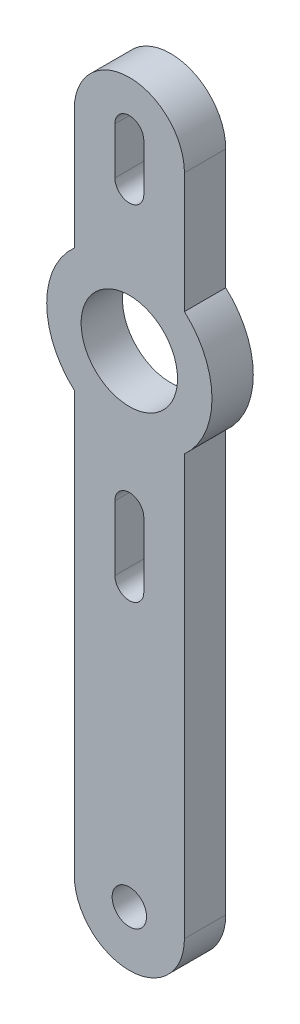
SolidWorks part; units mm, degrees
ref_plane "Plan de face" through (0, 0, 0) normal (0, 0, 1) x (1, 0, 0)
ref_plane "Plan de dessus" through (0, 0, 0) normal (0, 1, 0) x (1, 0, 0)
ref_plane "Plan de droite" through (0, 0, 0) normal (1, 0, 0) x (0, 0, -1)
sketch "Esquisse1" plane through (0, 0, 0) normal (0, 0, 1) x (1, 0, 0)
  line L0 (316.2402, 1609.0162) -> (317.0043, 1552.8214) construction
  line L1 (312.5454, 1587.3485) -> (312.5454, 1556.8582)
  line L2 (312.5454, 1605.0247) -> (312.5454, 1596.2927)
  line L3 (320.5454, 1587.3485) -> (320.5454, 1556.8582)
  line L4 (320.5454, 1605.0247) -> (320.5454, 1596.2927)
  line L5 (312.5454, 1580.4454) -> (320.5454, 1580.4454) construction
  line L6 (316.5454, 1580.4454) -> (316.5454, 1612.014) construction
  line L7 (316.5454, 1580.4454) -> (316.5454, 1554.1767) construction
  line L8 (316.5454, 1605.0247) -> (316.5454, 1602.7247) construction
  line L9 (318.1454, 1605.0247) -> (318.1454, 1602.7247) construction
  line L10 (314.9454, 1605.0247) -> (314.9454, 1602.7247) construction
  line L11 (315.4954, 1605.5747) -> (315.4954, 1602.1747)
  line L12 (315.4954, 1606.6247) -> (317.5954, 1606.6247) construction
  line L13 (315.4954, 1606.6247) -> (315.4954, 1601.1247) construction
  line L14 (315.4954, 1601.1247) -> (317.5954, 1601.1247) construction
  line L15 (317.5954, 1606.6247) -> (317.5954, 1601.1247) construction
  line L16 (317.5954, 1605.5747) -> (317.5954, 1602.1747)
  line L17 (315.4954, 1581.8706) -> (315.4954, 1577.1706)
  line L18 (315.4954, 1582.9206) -> (317.5954, 1582.9206) construction
  line L19 (315.4954, 1582.9206) -> (315.4954, 1576.1206) construction
  line L20 (315.4954, 1576.1206) -> (317.5954, 1576.1206) construction
  line L21 (317.5954, 1582.9206) -> (317.5954, 1576.1206) construction
  line L22 (317.5954, 1581.8706) -> (317.5954, 1577.1706)
  circle A0 centre (316.5454, 1605.0247) radius 4 construction
  circle A1 centre (316.5454, 1591.8206) radius 3.5
  circle A2 centre (316.5454, 1591.8206) radius 6 construction
  circle A3 centre (316.5454, 1556.8582) radius 1.25
  circle A4 centre (316.5454, 1556.8582) radius 4 construction
  arc A5 (312.5454, 1596.2927) -> (312.5454, 1587.3485) centre (316.5454, 1591.8206) ccw
  arc A6 (320.5454, 1596.2927) -> (320.5454, 1587.3485) centre (316.5454, 1591.8206) cw
  arc A7 (312.5454, 1605.0247) -> (320.5454, 1605.0247) centre (316.5454, 1605.0247) cw
  arc A8 (312.5454, 1556.8582) -> (320.5454, 1556.8582) centre (316.5454, 1556.8582) ccw
  arc A9 (318.1454, 1605.0247) -> (314.9454, 1605.0247) centre (316.5454, 1605.0247) ccw construction
  arc A10 (314.9454, 1602.7247) -> (318.1454, 1602.7247) centre (316.5454, 1602.7247) ccw construction
  arc A11 (317.5954, 1605.5747) -> (315.4954, 1605.5747) centre (316.5454, 1605.5747) ccw
  arc A13 (315.4954, 1602.1747) -> (317.5954, 1602.1747) centre (316.5454, 1602.1747) ccw
  arc A14 (317.5954, 1581.8706) -> (315.4954, 1581.8706) centre (316.5454, 1581.8706) ccw
  arc A15 (315.4954, 1577.1706) -> (317.5954, 1577.1706) centre (316.5454, 1577.1706) ccw
  point P28 (316.5454, 1603.8747)
  point P38 (316.5454, 1609.0247)
  dimension "D5" = 8
  dimension "D6" = 7
  dimension "D7" = 12
  dimension "D9" = 2.5
  dimension "D10" = 8
  dimension "D13" = 2.1
  dimension "D14" = 2.4
  dimension "D18" = 2.1
  dimension "D1" = 56.2
  dimension "D2" = 312.5454
  dimension "D3" = 8
  dimension "D4" = 8
  dimension "D8" = 1591.8206
  dimension "D11" = 1556.8582
  dimension "D12" = 1605.0247
  dimension "D15" = 1.05
  dimension "D16" = 2.4
  dimension "D17" = 5.5
  dimension "D19" = 1.05
  dimension "D20" = 6.8
  dimension "D21" = 5.4
base flange "Tôle de base pliée1" sketch "Esquisse1" thickness 3 reverse thickness direction no parameters "D1"=1.5
sketch "Lignes de pliage1" [suppressed] plane through (0, 0, 0) normal (0, 1, 0) x (1, 0, 0)
sketch "Cube de visualisation1" [suppressed] plane through (0, 0, 0) normal (0, 1, 0) x (1, 0, 0)
sheet metal parameters "Tôlerie1" thickness 3 parameters "D1"=1.5
flat pattern "Etat déplié1" [suppressed]
sketch "Lignes de pliage2" plane through (0, 0, 0) normal (0, 1, 0) x (1, 0, 0)
sketch3d "Cube de visualisation2" [suppressed]
  line L0 (3.7645, -39.1844, 0) -> (6.9732, 16.8108, 0) construction
  line L1 (-8.2159, -38.4979, 0) -> (-5.0072, 17.4973, 0) construction
  line L2 (3.7645, -39.1844, 0) -> (-8.2159, -38.4979, 0) construction
  line L3 (6.9732, 16.8108, 0) -> (-5.0072, 17.4973, 0) construction
